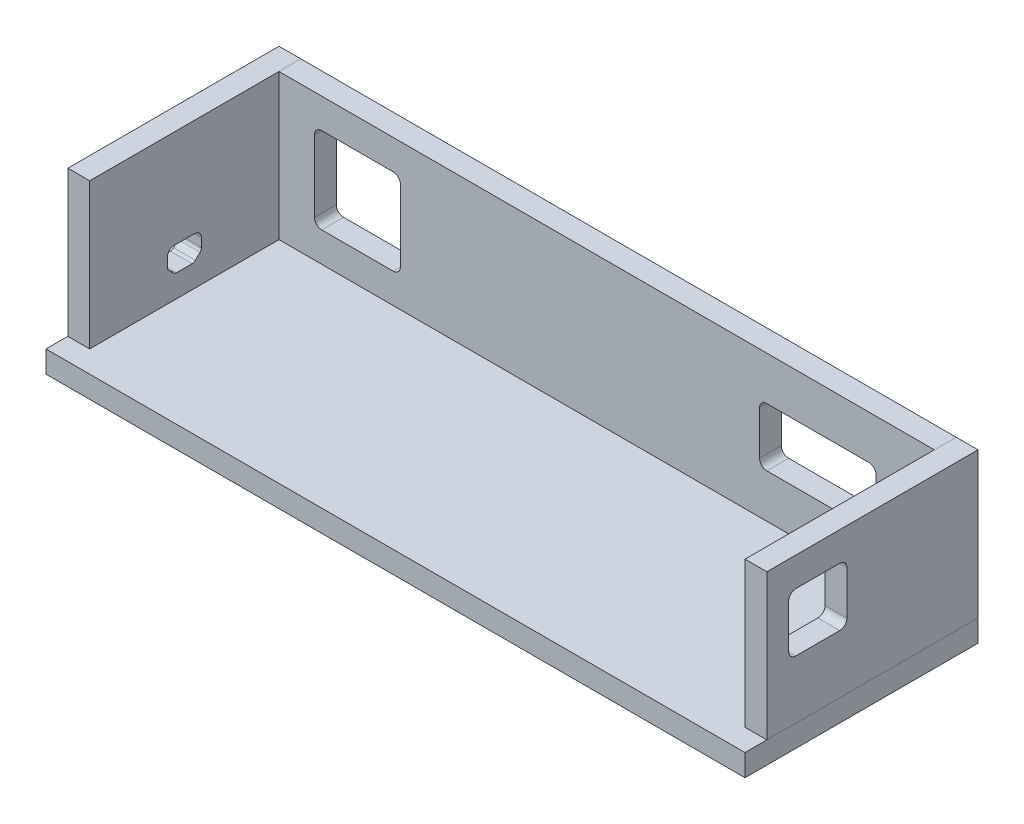
SolidWorks part; units mm, degrees
ref_plane "Front Plane" through (0, 0, 0) normal (0, 0, 1) x (1, 0, 0)
ref_plane "Top Plane" through (0, 0, 0) normal (0, 1, 0) x (1, 0, 0)
ref_plane "Right Plane" through (0, 0, 0) normal (1, 0, 0) x (0, 0, -1)
sketch "Sketch1" plane through (0, 0, 0) normal (0, 1, 0) x (1, 0, 0)
  line L1 (-304.8, 101.6) -> (304.8, 101.6)
  line L2 (-304.8, 101.6) -> (-304.8, -101.6)
  line L3 (-304.8, -101.6) -> (304.8, -101.6)
  line L4 (304.8, 101.6) -> (304.8, -101.6)
  line L5 (-304.8, 101.6) -> (304.8, -101.6) construction
  line L6 (-304.8, -101.6) -> (304.8, 101.6) construction
  point P0 (0, 0)
  dimension "D1" = 609.6
  dimension "D2" = 203.2
extrude "Boss-Extrude1" add sketch "Sketch1" along normal blind 19.05
sketch "Sketch2" plane through (0, 19.05, 0) normal (0, 1, 0) x (1, 0, 0)
  line L0 (-304.8, -101.6) -> (304.8, -101.6) construction
  line L1 (-304.8, 101.6) -> (-285.75, 101.6)
  line L2 (-304.8, 101.6) -> (-304.8, -101.6)
  line L3 (-304.8, -101.6) -> (-285.75, -101.6)
  line L4 (-285.75, 101.6) -> (-285.75, -101.6)
  line L5 (304.8, 101.6) -> (-304.8, 101.6) construction
  line L6 (304.8, -101.6) -> (285.75, -101.6)
  line L7 (304.8, -101.6) -> (304.8, 101.6)
  line L8 (304.8, 101.6) -> (285.75, 101.6)
  line L9 (285.75, -101.6) -> (285.75, 101.6)
  line L11 (-285.75, 101.6) -> (285.75, 101.6)
  line L12 (-285.75, 101.6) -> (-285.75, 82.55)
  line L13 (-285.75, 82.55) -> (285.75, 82.55)
  line L14 (285.75, 101.6) -> (285.75, 82.55)
  line M7 (304.8, -101.6) -> (304.8, 101.6)
  line M8 (304.8, 101.6) -> (-304.8, 101.6)
  line M9 (-304.8, 101.6) -> (-304.8, -101.6)
  line M10 (-304.8, -101.6) -> (304.8, -101.6)
  dimension "D1" = 19.05
  dimension "D2" = 19.05
  dimension "D3" = 19.05
extrude "Boss-Extrude2" add sketch "Sketch2" along normal blind 127 separate body contours L4 M8 M9 M10 | L9 M10 M7 M8 region at (-295.275, 19.05, 0) region at (295.275, 19.05, 0)
extrude "Boss-Extrude3" add sketch "Sketch2<3>" along normal up to surface (127 mm away) separate body contours L4 L13 L9 M8 region at (0, 19.05, -92.075) up to face at (-295.275, 146.05, 0)
sketch "Sketch2<3>" plane through (0, 19.05, 0) normal (0, 1, 0) x (1, 0, 0) same geometry as "Sketch2"
sketch "Sketch4" plane through (0, 19.05, 0) normal (0, 1, 0) x (1, 0, 0)
  line L0 (285.75, -101.6) -> (285.75, 101.6) construction
  line L1 (-285.75, -101.6) -> (285.75, -101.6)
  line L2 (-285.75, -101.6) -> (-285.75, -82.55)
  line L3 (-285.75, -82.55) -> (285.75, -82.55)
  line L4 (285.75, -101.6) -> (285.75, -82.55)
  dimension "D1" = 19.05
extrude "Boss-Extrude5" add sketch "Sketch4" along normal blind 6.35 separate body
sketch "Sketch5" plane through (-304.8, 0, -304.8) normal (1, 0, 0) x (0, 0, -1)
  line L0 (-203.2, 82.55) -> (-406.4, 82.55) construction
  line L1 (-203.2, 146.05) -> (-203.2, 19.05) construction
  line L2 (-406.4, 146.05) -> (-406.4, 19.05) construction
  line L3 (-304.8, 82.55) -> (-304.8, 19.05) construction
  line L4 (-203.2, 19.05) -> (-406.4, 19.05) construction
  line L26 (-295.1743, 39.8975) -> (-291.0923, 43.9795)
  line L27 (-289.9361, 46.7691) -> (-289.9361, 54.4059)
  line L28 (-295.9636, 60.4385) -> (-313.5841, 60.4385)
  line L29 (-319.6321, 54.3905) -> (-319.6321, 46.8124)
  line L30 (-318.4465, 43.95) -> (-314.4246, 39.9281)
  line L31 (-311.5622, 38.7425) -> (-309.7841, 38.7425)
  line L32 (-309.7841, 38.7425) -> (-299.7841, 38.7425)
  line L33 (-299.7841, 38.7425) -> (-297.9644, 38.7425)
  spline S18 degree 3 poles (-291.0923, 43.9795) (-291.0033, 44.0735) (-290.9158, 44.1689) (-290.7535, 44.3694) (-290.6774, 44.4737) (-290.4636, 44.7979) (-290.3426, 45.0263) (-290.1465, 45.4989) (-290.0705, 45.7454) (-289.9923, 46.1261) (-289.9724, 46.2537) (-289.9454, 46.5104) (-289.9398, 46.6397) (-289.9361, 46.7691) knots 0 0 0 0 0.125 0.125 0.25 0.25 0.5 0.5 0.75 0.75 0.875 0.875 1 1 1 1
  spline S19 degree 3 poles (-289.9361, 54.4059) (-289.9381, 54.6045) (-289.9467, 54.8019) (-289.9861, 55.1929) (-290.0151, 55.3868) (-290.0921, 55.7711) (-290.1401, 55.9616) (-290.2552, 56.3393) (-290.3228, 56.5272) (-290.5499, 57.0745) (-290.7344, 57.4205) (-291.1705, 58.0741) (-291.4251, 58.3841) (-291.9809, 58.9409) (-292.2833, 59.191) (-292.7753, 59.5217) (-292.9465, 59.6247) (-293.2946, 59.8114) (-293.4723, 59.8957) (-294.0155, 60.1225) (-294.3917, 60.2394) (-294.9766, 60.3577) (-295.1726, 60.3872) (-295.5666, 60.4274) (-295.7648, 60.4358) (-295.9636, 60.4385) knots 0 0 0 0 0.0625 0.0625 0.125 0.125 0.1875 0.1875 0.25 0.25 0.375 0.375 0.5 0.5 0.625 0.625 0.6875 0.6875 0.75 0.75 0.875 0.875 0.9375 0.9375 1 1 1 1
  spline S20 degree 3 poles (-313.5841, 60.4385) (-313.9834, 60.4385) (-314.376, 60.3998) (-314.9552, 60.2847) (-315.1466, 60.2368) (-315.5262, 60.1217) (-315.7149, 60.0541) (-316.2641, 59.827) (-316.6115, 59.6419) (-317.2686, 59.2036) (-317.5795, 58.9479) (-318.1377, 58.3905) (-318.3886, 58.0866) (-318.7204, 57.5913) (-318.8233, 57.4195) (-319.0098, 57.0704) (-319.094, 56.8921) (-319.3205, 56.3466) (-319.4373, 55.9666) (-319.5935, 55.185) (-319.6321, 54.7899) (-319.6321, 54.3905) knots 0 0 0 0 0.125 0.125 0.1875 0.1875 0.25 0.25 0.375 0.375 0.5 0.5 0.625 0.625 0.6875 0.6875 0.75 0.75 0.875 0.875 1 1 1 1
  spline S21 degree 3 poles (-319.6321, 46.8124) (-319.6321, 46.5457) (-319.6061, 46.2818) (-319.5017, 45.7593) (-319.4244, 45.5064) (-319.2237, 45.0204) (-319.0984, 44.7849) (-318.8033, 44.3432) (-318.6351, 44.1386) (-318.4465, 43.95) knots 0 0 0 0 0.25 0.25 0.5 0.5 0.75 0.75 1 1 1 1
  spline S22 degree 3 poles (-314.4246, 39.9281) (-314.236, 39.7395) (-314.0309, 39.5713) (-313.5877, 39.2757) (-313.3542, 39.1515) (-312.8686, 38.9498) (-312.6135, 38.8719) (-312.0925, 38.7682) (-311.8289, 38.7425) (-311.5622, 38.7425) knots 0 0 0 0 0.25 0.25 0.5 0.5 0.75 0.75 1 1 1 1
  spline S23 degree 3 poles (-297.9644, 38.7425) (-297.8349, 38.746) (-297.7057, 38.7516) (-297.4491, 38.7786) (-297.3215, 38.7985) (-296.9411, 38.8766) (-296.6941, 38.9525) (-296.2213, 39.1481) (-295.9932, 39.2686) (-295.6687, 39.4825) (-295.5644, 39.5587) (-295.3638, 39.7211) (-295.2684, 39.8086) (-295.1743, 39.8975) knots 0 0 0 0 0.125 0.125 0.25 0.25 0.5 0.5 0.75 0.75 0.875 0.875 1 1 1 1
  point P11 (-304.7739, 60.4385)
extrude "Cut-Extrude1" cut sketch "Sketch5" along normal up to surface (19.05 mm away) up to face at (-285.75, 82.55, 0)
sketch "Sketch6" plane through (0, 0, -82.55) normal (0, 0, 1) x (1, 0, 0)
  line L0 (-285.75, 146.05) -> (285.75, 146.05) construction
  line L1 (133.35, 107.95) -> (234.95, 107.95)
  line L2 (133.35, 107.95) -> (133.35, 57.15)
  line L3 (133.35, 57.15) -> (234.95, 57.15)
  line L4 (234.95, 107.95) -> (234.95, 57.15)
  line L5 (133.35, 107.95) -> (234.95, 57.15) construction
  line L6 (133.35, 57.15) -> (234.95, 107.95) construction
  line L7 (285.75, 146.05) -> (285.75, 19.05) construction
  point P0 (184.15, 82.55)
  dimension "D1" = 63.5
  dimension "D2" = 50.8
  dimension "D3" = 101.6
  dimension "D4" = 50.8
extrude "Cut-Extrude2" cut sketch "Sketch6" against normal through all
sketch "Sketch9" plane through (0, 0, -82.55) normal (0, 0, 1) x (1, 0, 0)
  line L0 (-285.75, 19.05) -> (285.75, 19.05) construction
  line L1 (-254.8532, 120.05) -> (-179.8532, 120.05)
  line L2 (-254.8532, 120.05) -> (-254.8532, 45.05)
  line L3 (-254.8532, 45.05) -> (-179.8532, 45.05)
  line L4 (-179.8532, 120.05) -> (-179.8532, 45.05)
  line L5 (-254.8532, 120.05) -> (-179.8532, 45.05) construction
  line L6 (-254.8532, 45.05) -> (-179.8532, 120.05) construction
  point P0 (-217.3532, 82.55)
  dimension "D1" = 75
  dimension "D2" = 75
  dimension "D3" = 63.5
extrude "Cut-Extrude3" cut sketch "Sketch9" against normal through all
sketch "Sketch10" plane through (285.75, 0, 0) normal (-1, 0, 0) x (0, 0, 1)
  line L0 (101.6, 146.05) -> (-101.6, 146.05) construction
  line L1 (12.7, 120.65) -> (63.5, 120.65)
  line L2 (12.7, 120.65) -> (12.7, 69.85)
  line L3 (12.7, 69.85) -> (63.5, 69.85)
  line L4 (63.5, 120.65) -> (63.5, 69.85)
  line L5 (12.7, 120.65) -> (63.5, 69.85) construction
  line L6 (12.7, 69.85) -> (63.5, 120.65) construction
  line L7 (101.6, 146.05) -> (101.6, 19.05) construction
  point P0 (38.1, 95.25)
  dimension "D1" = 50.8
  dimension "D2" = 50.8
  dimension "D3" = 50.8
  dimension "D5" = 38.1
extrude "Cut-Extrude4" cut sketch "Sketch10" against normal through all
fillet "Fillet1" radius 6.35 8 edges at (234.95, 107.95, -92.075) (234.95, 57.15, -92.075) (133.35, 57.15, -92.075) (133.35, 107.95, -92.075) (-254.8532, 45.05, -92.075) (-179.8532, 45.05, -92.075) (-254.8532, 120.05, -92.075) (-179.8532, 120.05, -92.075)
fillet "Fillet2" radius 6.35 4 edges at (295.275, 120.65, 63.5) (295.275, 69.85, 63.5) (295.275, 69.85, 12.7) (295.275, 120.65, 12.7)
sketch "Sketch11" plane through (-304.8, 0, 0) normal (-1, 0, 0) x (0, 0, 1)
  line L0 (-101.6, 146.05) -> (101.6, 146.05) construction
  line L1 (101.6, 19.05) -> (82.55, 19.05)
  line L2 (101.6, 19.05) -> (101.6, 146.05)
  line L3 (101.6, 146.05) -> (82.55, 146.05)
  line L4 (82.55, 19.05) -> (82.55, 146.05)
  dimension "D1" = 19.05
extrude "Cut-Extrude5" cut sketch "Sketch11" against normal through all
